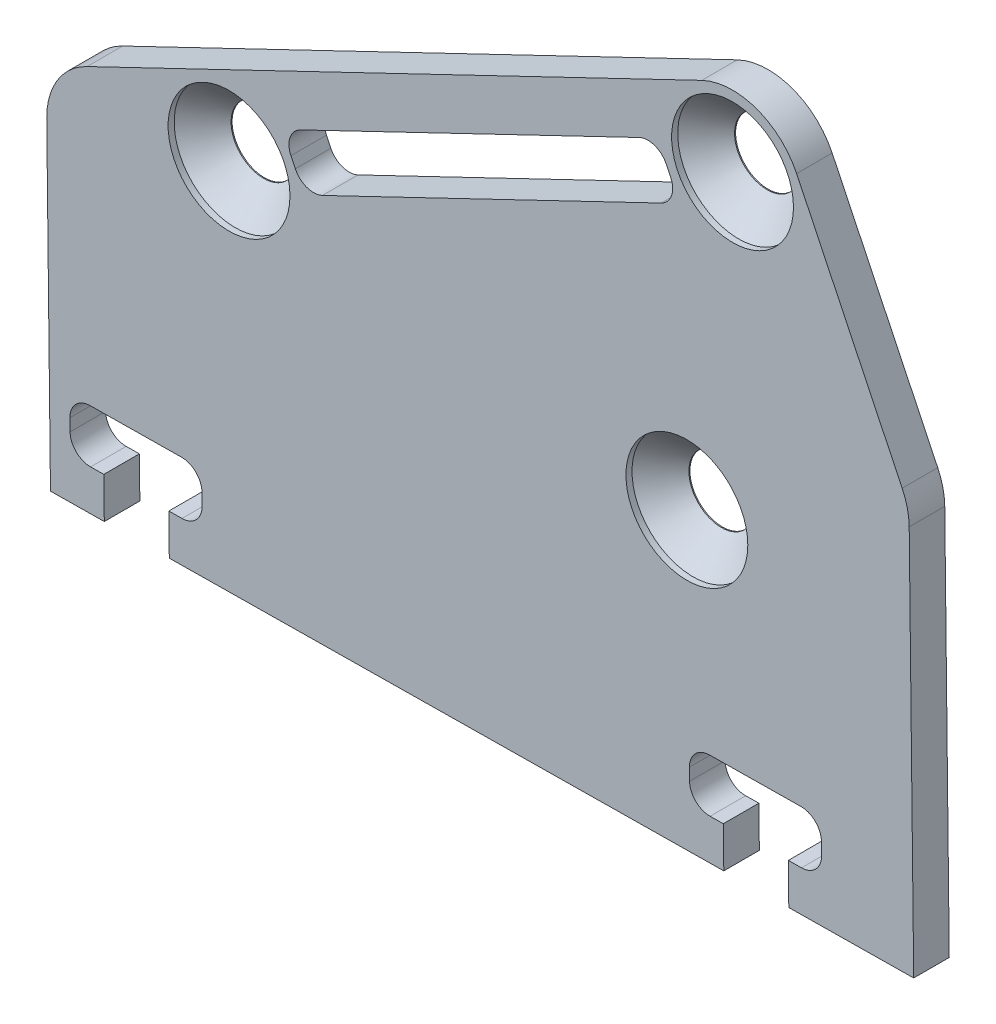
SolidWorks part; units mm, degrees
ref_plane "Front Plane" through (0, 0, 0) normal (0, 0, 1) x (1, 0, 0)
ref_plane "Top Plane" through (0, 0, 0) normal (0, 1, 0) x (1, 0, 0)
ref_plane "Right Plane" through (0, 0, 0) normal (1, 0, 0) x (0, 0, -1)
sketch "Sketch2" plane through (277.9441, -368.7823, 0) normal (0, 0, 1) x (0.9999, 0.0116, 0)
  line L0 (-273.6458, 371.9829) -> (-231.1458, 371.9829)
  line L1 (-236.5451, 403.462) -> (-231.4737, 392.5863)
  line L2 (-273.6458, 390.0235) -> (-231.1458, 390.0235) construction
  line L3 (-269.3958, 375.2829) -> (-238.8958, 375.2829) construction
  line L5 (-241.1964, 405.155) -> (-273.6458, 390.0235)
  line L6 (-273.6458, 390.0235) -> (-273.6458, 371.9829)
  line L8 (-264.6407, 390.3609) -> (-239.7172, 401.9829) construction
  line L9 (-260.034, 391.1298) -> (-243.2673, 398.9482)
  line L10 (-261.3629, 391.6135) -> (-261.5742, 392.0666)
  line L11 (-242.7836, 400.2771) -> (-242.9949, 400.7303)
  line L12 (-261.0905, 393.3955) -> (-244.3238, 401.214)
  line L13 (-260.9403, 390.7072) -> (-243.4175, 401.6366) construction
  line L14 (-270.1458, 387.7938) -> (-239.7172, 401.9829) construction
  line L15 (-242.361, 399.3708) -> (-261.9968, 392.9729) construction
  line L16 (-254.1458, 375.2829) -> (-254.1458, 371.9829) construction
  line L19 (-241.1458, 373.9829) -> (-236.6458, 373.9829)
  line L20 (-242.1458, 374.9829) -> (-242.1458, 375.5829)
  line L21 (-241.1458, 376.5829) -> (-236.6458, 376.5829)
  line L22 (-235.6458, 374.9829) -> (-235.6458, 375.5829)
  line L23 (-242.1458, 373.9829) -> (-235.6458, 376.5829) construction
  line L24 (-242.1458, 376.5829) -> (-235.6458, 373.9829) construction
  line L26 (-238.8958, 373.9829) -> (-238.8958, 371.9829) construction
  line L28 (-240.4958, 371.9829) -> (-237.2958, 371.9829)
  line L29 (-240.4958, 371.9829) -> (-240.4958, 373.9829)
  line L30 (-240.4958, 373.9829) -> (-237.2958, 373.9829)
  line L31 (-237.2958, 371.9829) -> (-237.2958, 373.9829)
  line L32 (-240.4958, 371.9829) -> (-237.2958, 373.9829) construction
  line L33 (-240.4958, 373.9829) -> (-237.2958, 371.9829) construction
  line L38 (-270.9958, 371.9829) -> (-270.9958, 373.9829)
  line L39 (-231.1458, 391.1072) -> (-231.1458, 371.9829)
  line L41 (-267.7958, 371.9829) -> (-267.7958, 373.9829)
  line L42 (-267.1458, 373.9829) -> (-271.6458, 373.9829)
  line L43 (-266.1458, 374.9829) -> (-266.1458, 375.5829)
  line L44 (-272.6458, 374.9829) -> (-272.6458, 375.5829)
  line L45 (-267.1458, 376.5829) -> (-271.6458, 376.5829)
  circle A0 centre (-242.1458, 386.4829) radius 1.6
  circle A1 centre (-264.6407, 390.3609) radius 1.6
  circle A2 centre (-239.7172, 401.9829) radius 1.6
  circle A3 centre (-270.1458, 387.7938) radius 3.5
  circle A4 centre (-239.7172, 401.9829) radius 3.5
  arc A5 (-261.5742, 392.0666) -> (-261.0905, 393.3955) centre (-260.6679, 392.4892) cw
  circle A6 centre (-234.6458, 391.1072) radius 3.5
  arc A7 (-241.1458, 373.9829) -> (-242.1458, 374.9829) centre (-241.1458, 374.9829) cw
  arc A8 (-236.6458, 373.9829) -> (-235.6458, 374.9829) centre (-236.6458, 374.9829) ccw
  arc A9 (-236.6458, 376.5829) -> (-235.6458, 375.5829) centre (-236.6458, 375.5829) cw
  arc A10 (-242.1458, 375.5829) -> (-241.1458, 376.5829) centre (-241.1458, 375.5829) cw
  arc A11 (-261.3629, 391.6135) -> (-260.034, 391.1298) centre (-260.4566, 392.0361) ccw
  arc A12 (-243.2673, 398.9482) -> (-242.7836, 400.2771) centre (-243.6899, 399.8545) ccw
  arc A13 (-271.6458, 373.9829) -> (-272.6458, 374.9829) centre (-271.6458, 374.9829) cw
  arc A14 (-267.1458, 373.9829) -> (-266.1458, 374.9829) centre (-267.1458, 374.9829) ccw
  arc A15 (-266.1458, 375.5829) -> (-267.1458, 376.5829) centre (-267.1458, 375.5829) ccw
  arc A16 (-271.6458, 376.5829) -> (-272.6458, 375.5829) centre (-271.6458, 375.5829) ccw
  arc A17 (-242.9949, 400.7303) -> (-244.3238, 401.214) centre (-243.9012, 400.3077) ccw
  point P4 (-250.5394, 391.8894)
  point P10 (-252.1789, 396.1719)
  point P15 (-239.7172, 401.9829)
  point P21 (-264.3918, 382.1899)
  point P22 (-263.6458, 382.7122)
  point P28 (-263.6458, 382.7122)
  point P29 (-245.5642, 397.648)
  point P51 (-238.8958, 372.9829)
  point P64 (-273.6458, 382.4566)
  dimension "D1" = 3.2
  dimension "D10" = 1
  dimension "D13" = 20.5
  dimension "D2" = 7
  dimension "D17" = 1
  dimension "D3" = 30
  dimension "D4" = 12
  dimension "D5" = 30.5
  dimension "D6" = 4.25
  dimension "D7" = 2.6
  dimension "D8" = 6.5
  dimension "D9" = 2
  dimension "D11" = 3.2
  dimension "D12" = 2.5
  dimension "D14" = 4.5
  dimension "D15" = 25
  dimension "D16" = 14.5
  dimension "D18" = 12
extrude "Boss-Extrude1" add sketch "Sketch2" along normal blind 1.75 contours A17 L11 A4 L5 A3 L6 L0 L38 L42 A13 L44 A16 L45 A15 L43 A14 L41 L29 L19 A7 L20 A10 L21 A9 L22 A8 L31 L39 A6 L1 A12 L9 A11 L10 A5 L12 A1 A0 | A3 | A6 | A4 A2 region at (22.6531, 12.7534, 0) region at (3.3163, 15.8505, 0) region at (34.7042, 33.6009, 0) region at (38.7754, 19.5756, 0)
sketch "Sketch3" plane through (0, 0, 1.75) normal (0, 0, 1) x (1, 0, 0)
  circle A0 centre (8.7912, 18.4813) radius 3
  circle A1 centre (31.3296, 14.8646) radius 3
  circle A2 centre (33.5782, 30.3917) radius 3
  dimension "D1" = 6
extrude "Cut-Extrude2" cut sketch "Sketch3" against normal blind 0.3
chamfer "Chamfer1" distance 1.4 angle 45 3 edges at (10.3912, 18.4813, 1.45) (32.9296, 14.8646, 1.45) (35.1782, 30.3917, 1.45)
